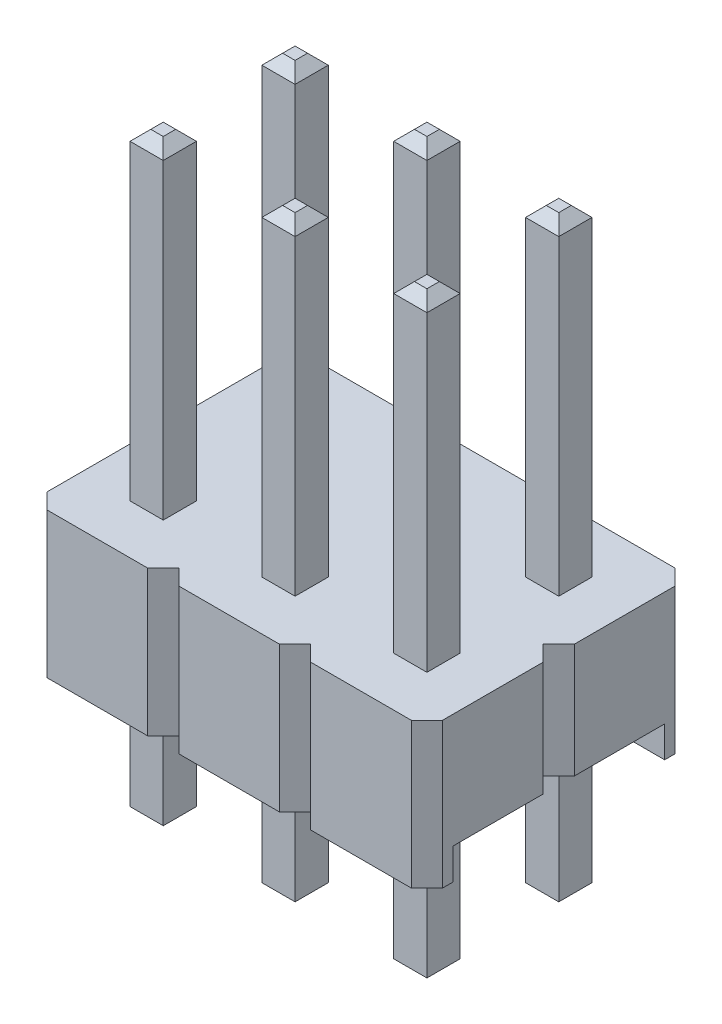
SolidWorks part; units mm, degrees
ref_plane "Front Plane" through (0, 0, 0) normal (0, 0, 1) x (1, 0, 0)
ref_plane "Top Plane" through (0, 0, 0) normal (0, 1, 0) x (1, 0, 0)
ref_plane "Right Plane" through (0, 0, 0) normal (1, 0, 0) x (0, 0, -1)
sketch "Sketch1" plane through (0, 0, 0) normal (0, 1, 0) x (1, 0, 0)
  line L0 (-1000, 0) -> (49000, 0) construction
  line L55 (-2.86, 1.59) -> (-2.22, 1.59)
  line L56 (-2.86, 1.59) -> (-2.86, 0.95)
  line L57 (-2.86, 0.95) -> (-2.22, 0.95)
  line L58 (-2.22, 1.59) -> (-2.22, 0.95)
  line L59 (-2.86, 1.59) -> (-2.22, 0.95) construction
  line L60 (-2.86, 0.95) -> (-2.22, 1.59) construction
  line L61 (0, -1000) -> (0, 49000) construction
  line L62 (-3.81, 2.24) -> (-3.51, 2.54)
  line L63 (-3.51, 2.54) -> (-1.57, 2.54)
  line L64 (-3.81, 2.24) -> (-3.81, 0.3)
  line L67 (3.81, 2.24) -> (3.81, 0.3)
  line L68 (3.81, 0.3) -> (3.51, 0)
  line L69 (-1.57, 2.54) -> (-1.27, 2.24)
  line L71 (-3.81, 0.3) -> (-3.51, 0)
  line L72 (-1.27, 2.24) -> (-0.97, 2.54)
  line L73 (-0.97, 2.54) -> (0.97, 2.54)
  line L74 (0.97, 2.54) -> (1.27, 2.24)
  line L75 (3.81, -0.3) -> (3.81, -2.24)
  line L76 (3.81, -2.24) -> (3.51, -2.54)
  line L77 (1.27, 2.24) -> (1.57, 2.54)
  line L78 (1.57, 2.54) -> (3.51, 2.54)
  line L79 (3.51, 2.54) -> (3.81, 2.24)
  line L80 (-1.27, -2.24) -> (-0.97, -2.54)
  line L81 (-1.27, -2.24) -> (-1.57, -2.54)
  line L82 (1.27, -2.24) -> (0.97, -2.54)
  line L83 (-3.51, -2.54) -> (-1.57, -2.54)
  line L84 (-0.97, -2.54) -> (0.97, -2.54)
  line L85 (1.27, -2.24) -> (1.57, -2.54)
  line L86 (1.57, -2.54) -> (3.51, -2.54)
  line L87 (-0.32, 0.95) -> (0.32, 0.95)
  line L88 (-0.32, 1.59) -> (-0.32, 0.95)
  line L89 (3.51, 0) -> (3.81, -0.3)
  line L90 (-3.81, -2.24) -> (-3.51, -2.54)
  line L91 (-3.81, -0.3) -> (-3.81, -2.24)
  line L92 (-3.81, -0.3) -> (-3.51, 0)
  line L93 (-0.32, 1.59) -> (0.32, 1.59)
  line L94 (0.32, 1.59) -> (0.32, 0.95)
  line L95 (-3.81, 0.3) -> (-1.27, 0.3) construction
  line L96 (-3.51, 0) -> (-1.57, 0) [skipped]
  line L97 (-1.57, 0) -> (-1.27, -0.3) [skipped]
  line L98 (-1.27, -0.3) -> (-0.97, 0) [skipped]
  line L99 (-1.27, 0.3) -> (-0.97, 0) [skipped]
  line L100 (-1.27, 2.24) -> (-1.27, 0.3) [skipped]
  line L101 (-1.27, -0.3) -> (-1.27, -2.24) [skipped]
  line L102 (1.27, -0.3) -> (1.27, -2.24) [skipped]
  line L103 (0.97, 0) -> (1.27, -0.3) [skipped]
  line L104 (-0.97, 0) -> (0.97, 0) [skipped]
  line L105 (1.27, 2.24) -> (1.27, 0.3) [skipped]
  line L106 (1.27, 0.3) -> (1.57, 0) [skipped]
  line L107 (1.27, -0.3) -> (1.57, 0) [skipped]
  line L108 (1.57, 0) -> (3.51, 0) [skipped]
  line L109 (2.22, 0.95) -> (2.86, 0.95)
  line L110 (2.22, 1.59) -> (2.22, 0.95)
  line L111 (2.22, 1.59) -> (2.86, 1.59)
  line L112 (2.86, 1.59) -> (2.86, 0.95)
  line L113 (-0.32, -1.59) -> (0.32, -1.59)
  line L114 (-0.32, -0.95) -> (-0.32, -1.59)
  line L115 (-0.32, -0.95) -> (0.32, -0.95)
  line L116 (0.32, -0.95) -> (0.32, -1.59)
  line L117 (2.22, -1.59) -> (2.86, -1.59)
  line L118 (2.22, -0.95) -> (2.22, -1.59)
  line L119 (2.22, -0.95) -> (2.86, -0.95)
  line L120 (2.86, -0.95) -> (2.86, -1.59)
  line L121 (-2.86, -1.59) -> (-2.22, -1.59)
  line L122 (-2.86, -0.95) -> (-2.86, -1.59)
  line L123 (-2.86, -0.95) -> (-2.22, -0.95)
  line L124 (-2.22, -0.95) -> (-2.22, -1.59)
  line L125 (-2.86, 0.95) -> (-0.32, 0.95) construction
  point P0 (-2.54, 1.27)
  point P8 (-2.54, 1.27)
  dimension "D1" = 0.64
  dimension "D2" = 2.54
  dimension "D5" = 2
  dimension "D3" = 5.08
  dimension "D4" = 3
  dimension "D6" = 2.54
  dimension "D9" = 2.54
  dimension "D7" = 3
  dimension "D8" = 2
extrude "Boss-Extrude1" add sketch "Sketch1" along normal blind 2.8
sketch "Sketch2" plane through (0, 0, 0) normal (1, 0, 0) x (0, 0, -1)
  line L0 (-2.24, 0) -> (-0.3, 0) construction
  line L1 (-2.04, 0) -> (2.04, 0)
  line L2 (-2.04, 0) -> (-2.04, 0.6)
  line L3 (-2.04, 0.6) -> (2.04, 0.6)
  line L4 (2.04, 0) -> (2.04, 0.6)
  line L5 (-2.54, 2.8) -> (-2.54, 0) construction
  line L6 (0, -1000) -> (0, 49000) construction
  dimension "D1" = 0.5
  dimension "D2" = 0.6
extrude "Cut-Extrude1" cut sketch "Sketch2" against normal through all both and the other way through all
extrude "Boss-Extrude2" add sketch "Sketch1<2>" along normal blind 9 and the other way blind 2.5 separate body contours L57 L58 L55 L56 | L121 L124 L123 L122 | L113 L116 L115 L114 | L87 L94 L93 L88 | L109 L112 L111 L110 | L117 L120 L119 L118
sketch "Sketch1<2>" plane through (0, 0, 0) normal (0, 1, 0) x (1, 0, 0) same geometry as "Sketch1"
chamfer "Chamfer1" distance 0.2 angle 45 8 edges at (-2.54, -2.5, -0.95) (-2.22, -2.5, -1.27) (-2.54, -2.5, -1.59) (-2.86, -2.5, -1.27) (-2.54, 9, -1.59) (-2.22, 9, -1.27) (-2.54, 9, -0.95) (-2.86, 9, -1.27)
chamfer "Chamfer2" distance 0.2 angle 45 8 edges at (-2.54, -2.5, 1.59) (-2.22, -2.5, 1.27) (-2.54, -2.5, 0.95) (-2.86, -2.5, 1.27) (-2.54, 9, 0.95) (-2.22, 9, 1.27) (-2.54, 9, 1.59) (-2.86, 9, 1.27)
chamfer "Chamfer3" distance 0.2 angle 45 8 edges at (0, -2.5, 1.59) (0.32, -2.5, 1.27) (0, -2.5, 0.95) (-0.32, -2.5, 1.27) (0, 9, 0.95) (0.32, 9, 1.27) (0, 9, 1.59) (-0.32, 9, 1.27)
chamfer "Chamfer4" distance 0.2 angle 45 8 edges at (0, 9, -1.59) (0.32, 9, -1.27) (0, 9, -0.95) (-0.32, 9, -1.27) (0, -2.5, -0.95) (0.32, -2.5, -1.27) (0, -2.5, -1.59) (-0.32, -2.5, -1.27)
chamfer "Chamfer5" distance 0.2 angle 45 8 edges at (2.54, 9, 0.95) (2.86, 9, 1.27) (2.54, 9, 1.59) (2.22, 9, 1.27) (2.54, -2.5, 1.59) (2.86, -2.5, 1.27) (2.54, -2.5, 0.95) (2.22, -2.5, 1.27)
chamfer "Chamfer6" distance 0.2 angle 45 8 edges at (2.54, -2.5, -0.95) (2.86, -2.5, -1.27) (2.54, -2.5, -1.59) (2.22, -2.5, -1.27) (2.54, 9, -1.59) (2.86, 9, -1.27) (2.54, 9, -0.95) (2.22, 9, -1.27)
